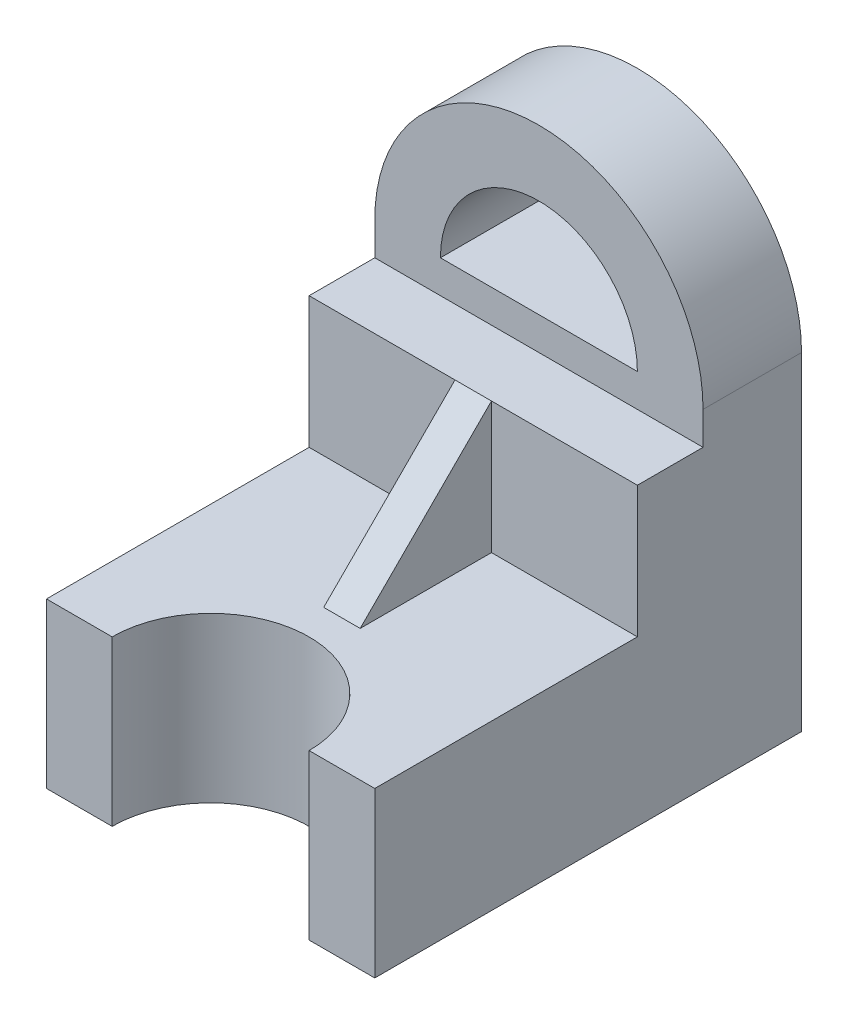
SolidWorks part; units mm, degrees
ref_plane "Front Plane" through (0, 0, 0) normal (0, 0, 1) x (1, 0, 0)
ref_plane "Top Plane" through (0, 0, 0) normal (0, 1, 0) x (1, 0, 0)
ref_plane "Right Plane" through (0, 0, 0) normal (1, 0, 0) x (0, 0, -1)
sketch "Sketch1" plane through (0, 0, 0) normal (0, 0, 1) x (1, 0, 0)
  line L0 (0, 0) -> (-21850.6365, 0) construction
  line L1 (0, 0) -> (0, 21850.6365) construction
  line L3 (0, 0) -> (90, 0)
  line L4 (0, 0) -> (0, 45)
  line L5 (0, 45) -> (68.4979, 45)
  line L6 (90, 0) -> (90, 45)
  line L7 (0, 45) -> (90, 45)
  line L8 (0, 45) -> (0, 81)
  line L9 (0, 81) -> (90, 81)
  line L10 (90, 45) -> (90, 81)
  line L19 (0, 81) -> (90, 81)
  line L20 (0, 81) -> (0, 90)
  line L21 (0, 90) -> (90, 90)
  line L22 (90, 81) -> (90, 90)
  arc A3 (90, 90) -> (0, 90) centre (45, 90) ccw
  arc A4 (72, 90) -> (18, 90) centre (45, 90) ccw
  dimension "D1" = 90
  dimension "D5" = 54
  dimension "D2" = 45
  dimension "D3" = 36
  dimension "D4" = 9
  dimension "D6" = 90
extrude "Boss-Extrude1" add sketch "Sketch1" against normal blind 117 contours L3 L6 L5 L4 region at (45, 22.5, 0)
extrude "Boss-Extrude2" add sketch "Sketch1<3>" against normal blind 45 from offset 72 contours L5 L10 L9 L8 region at (45, 63, 0) offset against normal yes
sketch "Sketch1<3>" plane through (0, 0, 0) normal (0, 0, 1) x (1, 0, 0) same geometry as "Sketch1"
extrude "Boss-Extrude4" add sketch "Sketch1<5>" against normal blind 27 from offset 90 contours L9 L22 L21 L20 region at (45, 85.5, 0) offset against normal yes
sketch "Sketch1<5>" plane through (0, 0, 0) normal (0, 0, 1) x (1, 0, 0) same geometry as "Sketch1"
extrude "Boss-Extrude5" add sketch "Sketch1<6>" against normal blind 27 from offset 90 contours A4 L21 A3 region at (45, 133.9938, 0) offset against normal yes
sketch "Sketch1<6>" plane through (0, 0, 0) normal (0, 0, 1) x (1, 0, 0) same geometry as "Sketch1"
sketch "Sketch2" plane through (0, 45, 0) normal (0, 1, 0) x (1, 0, 0)
  line L0 (0, 0) -> (90, 0) construction
  line L1 (18, 0) -> (72, 0)
  arc A0 (72, 0) -> (18, 0) centre (45, 0) ccw
  dimension "D1" = 54
extrude "Cut-Extrude1" cut sketch "Sketch2" against normal through all
ref_plane "Plane1" through (45, 0, 0) normal (1, 0, 0) x (0, 0, -1)
sketch "Sketch5" plane through (45, 0, 0) normal (1, 0, 0) x (0, 0, -1)
  line L0 (72, 81) -> (36, 45)
  line L1 (72, 45) -> (72, 81) construction
  line L2 (72, 45) -> (0, 45) construction
  dimension "D1" = 36
  dimension "D2" = 36
rib "Rib4" sketch "Sketch5" sketch "Sketch5" thickness 10 extrusion direction parallel to sketch draft on no parameters "D1"=10
